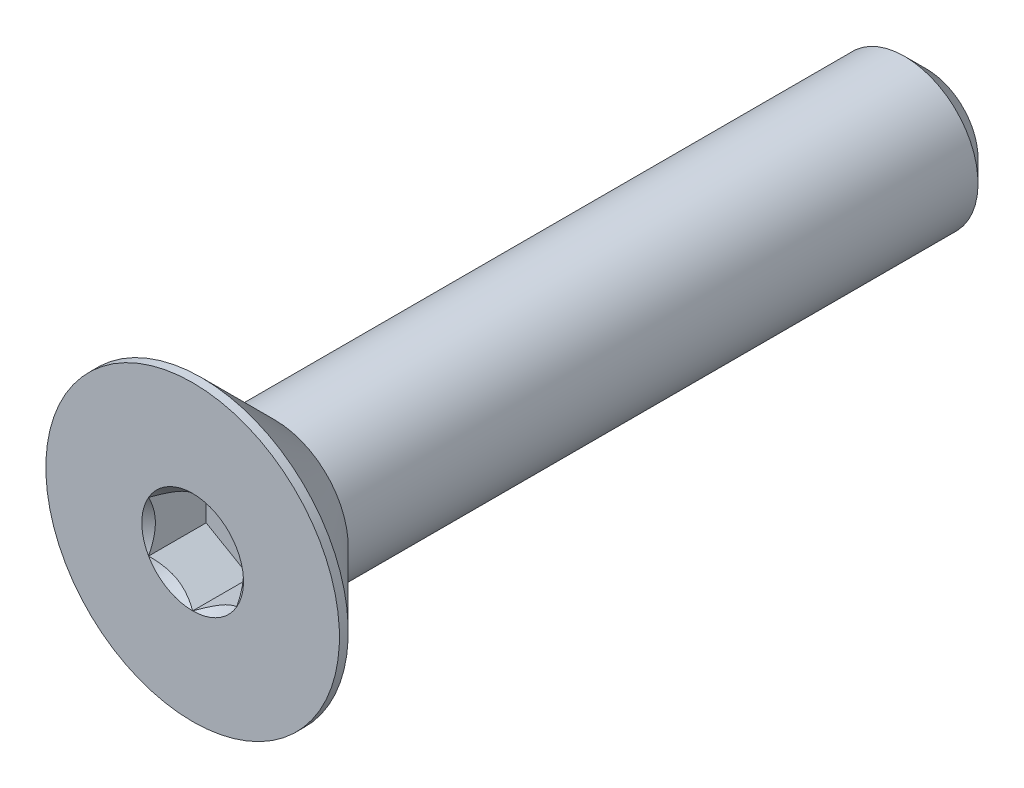
SolidWorks part; units mm, degrees
material "Alloy Steel"
ref_plane "Front" through (0, 0, 0) normal (0, 0, 1) x (1, 0, 0)
ref_plane "Top" through (0, 0, 0) normal (0, 1, 0) x (1, 0, 0)
ref_plane "Right" through (0, 0, 0) normal (1, 0, 0) x (0, 0, -1)
sketch "Sketch1" plane through (0, 0, 0) normal (1, 0, 0) x (0, 0, -1)
  line L0 (-12.5, 5) -> (-12.2, 5) construction
  line L1 (-12.2, 5) -> (-9.7, 2.5) construction
  line L2 (-12.5, 2.5) -> (12.5, 2.5) construction
  line L3 (12.5, 2.5) -> (12.5, 0) construction
  line L4 (12.5, 0) -> (-12.5, 0) construction
  line L5 (-12.5, 0) -> (-12.5, 5) construction
  line L6 (-12.5, 5) -> (-12.5, -5) construction
  line L7 (12.5, 2.5) -> (12.5, -2.5) construction
  line L8 (-12.5, -5) -> (-12.2, -5) construction
  line L9 (-12.2, -5) -> (-9.7, -2.5) construction
  line L11 (-12.5, 2.5) -> (-12.5, 0) construction
  line L12 (-9.7, 2.5) -> (-9.7, 0) construction
  line L13 (12.45, 2.5866) -> (12.85, 1.8938) construction
  line L14 (12.85, 1.8938) -> (13.25, 2.5866) construction
  line L15 (13.25, 2.5866) -> (12.45, 2.5866) construction
  line L16 (12.85, 2.5866) -> (12.85, 2.5) construction
  line L17 (12.85, 2.5) -> (12.85, 1.9804) construction
  line L18 (12.85, 1.9804) -> (12.85, 1.8938) construction
  line L19 (12.85, 2.5433) -> (13.225, 2.5433) construction
  line L20 (12.85, 2.5433) -> (12.475, 2.5433) construction
  line L21 (12.5, 2.5) -> (13.2, 2.5) construction
  line L22 (12.8, 1.9804) -> (12.9, 1.9804) construction
  line L23 (12.5, -2.5) -> (-9.7, -2.5) construction
  point P10 (10.5, -2.5)
  point P24 (-9.7, 2.5)
  point P30 (0, 0)
  dimension "Head Diameter" = 10
  dimension "Head Height" = 2.8
  dimension "Length" = 25
  dimension "Countersink Angle" = 90
  dimension "Thread Pitch" = 0.8
  dimension "D2" = 0.1
  dimension "Minimum Thread Length" = 22.2
  dimension "Thread Size" = 5
  dimension "D1" = 2
sketch "Sketch2" plane through (0, 0, 0) normal (0, 0, 1) x (1, 0, 0)
  line L1 (0, 1.7321) -> (-1.5, 0.866) construction
  line L2 (-1.5, 0.866) -> (-1.5, -0.866) construction
  line L3 (-1.5, -0.866) -> (0, -1.7321) construction
  line L4 (0, -1.7321) -> (1.5, -0.866) construction
  line L5 (1.5, -0.866) -> (1.5, 0.866) construction
  line L6 (1.5, 0.866) -> (0, 1.7321) construction
  circle A0 centre (0, 0) radius 1.5 construction
  dimension "Drive Size" = 3
sketch "Sketch3" plane through (0, 0, 0) normal (1, 0, 0) x (0, 0, -1)
  line L0 (-12.5, 2.5) -> (12.5, 2.5)
  line L1 (12.5, 2.5) -> (12.5, 0)
  line L2 (12.5, 0) -> (-12.5, 0)
  line L3 (-12.5, 0) -> (-12.5, 2.5)
revolve "Revolve1" add sketch "Sketch3" angle 360 about L4
chamfer "Chamfer1" distance 0.75 angle 45 1 edges at (0, 2.5, -12.5)
sketch "Sketch6" plane through (0, 0, 0) normal (1, 0, 0) x (0, 0, -1)
  line L0 (-12.5, 5) -> (-12.2, 5)
  line L1 (-12.2, 5) -> (-9.7, 2.5)
  line L2 (-9.7, 2.5) -> (-9.7, 0)
  line L3 (-9.7, 0) -> (-12.5, 0)
  line L4 (-12.5, 0) -> (-12.5, 5)
revolve "Revolve2" add sketch "Sketch6" angle 360 about L4
sketch "Sketch8" plane through (0, 0, 12.5) normal (0, 0, 1) x (1, 0, 0)
  line L0 (0, 1.7321) -> (-1.5, 0.866) construction
  line L1 (1.5, 0.866) -> (0, 1.7321) construction
  line L2 (1.5, -0.866) -> (1.5, 0.866) construction
  line L3 (0, -1.7321) -> (1.5, -0.866) construction
  line L4 (-1.5, 0.866) -> (-1.5, -0.866) construction
  line L5 (-1.5, -0.866) -> (0, -1.7321) construction
  line L6 (0, 1.7321) -> (-1.5, 0.866)
  line L7 (1.5, 0.866) -> (0, 1.7321)
  line L8 (1.5, -0.866) -> (1.5, 0.866)
  line L9 (0, -1.7321) -> (1.5, -0.866)
  line L10 (-1.5, 0.866) -> (-1.5, -0.866)
  line L11 (-1.5, -0.866) -> (0, -1.7321)
extrude "Cut-Extrude1" cut sketch "Sketch8" against normal blind 1.96
sketch "Sketch9" plane through (0, 0, 12.5) normal (0, 0, 1) x (1, 0, 0)
  circle A0 centre (0, 0) radius 1.7321
extrude "Cut-Extrude2" cut sketch "Sketch9" against normal up to next (1.96 mm away) draft 45
ref_plane "Plane1" [suppressed] through (0, 0, 9.7) normal (0, 0, 1) x (1, 0, 0)
split "Split1" [suppressed] bodies to split 124
sketch "Sketch4" [suppressed] plane through (0, 0, -12.5) normal (0, 0, -1) x (-1, 0, 0)
  circle A0 centre (0, 0) radius 2.5 construction
  circle A1 centre (0, 0) radius 2.5
curve "Helix/Spiral1" [suppressed] pitch 0.8 height 23 turns 28.75
sketch "Sketch10" [suppressed] plane through (0, 0, 0) normal (1, 0, 0) x (0, 0, -1)
  line L0 (12.475, 2.5433) -> (13.225, 2.5433)
  line L1 (13.225, 2.5433) -> (12.9, 1.9804)
  line L2 (12.9, 1.9804) -> (12.8, 1.9804)
  line L3 (12.8, 1.9804) -> (12.475, 2.5433)
sweep "Cut-Sweep1" [suppressed] cut profiles "Sketch10" path "Helix/Spiral1"
equation "\"D2@Sketch1\" = \"Thread Pitch@Sketch1\" / 8"
equation "\"D4@Helix/Spiral1\"=\"Thread Pitch@Sketch1\""
equation "\"D3@Helix/Spiral1\"=\"Minimum Thread Length@Sketch1\"+\"Thread Pitch@Sketch1\""
equation "\"D1@Chamfer1\"=\"Thread Size@Sketch1\"*.15"
equation "\"D1@Cut-Extrude1\"=\"Head Height@Sketch1\"*.7"
equation "\"D1@Sketch1\"=\"Thread Pitch@Sketch1\"*2.5"
